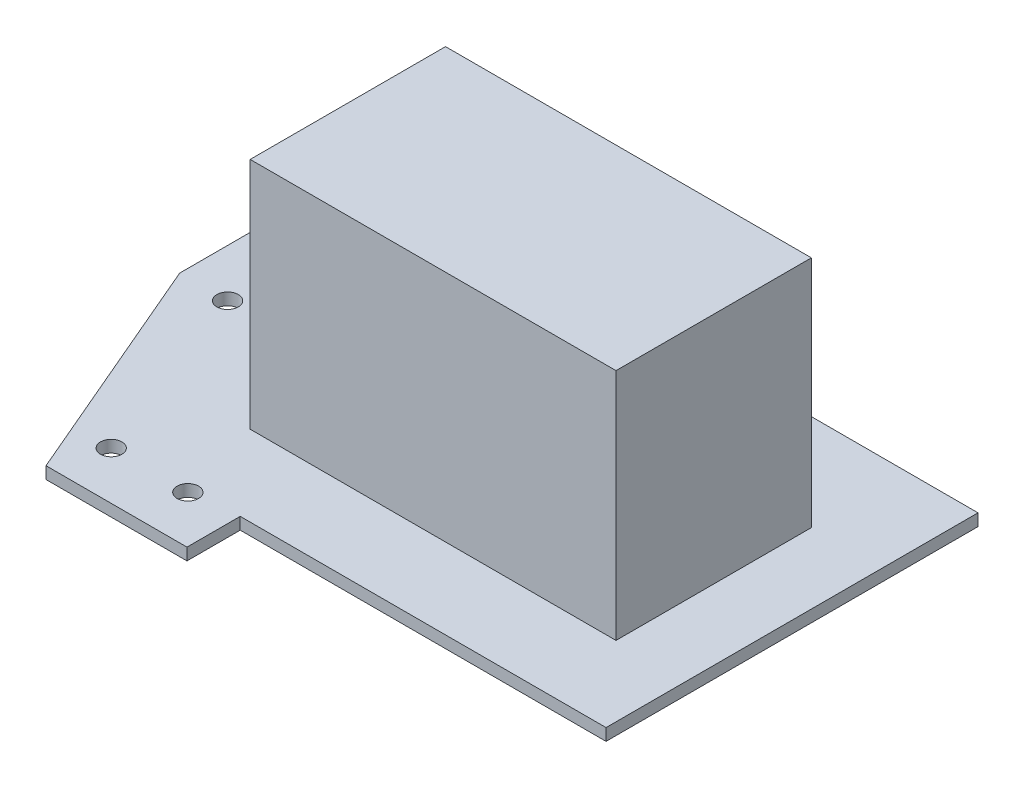
SolidWorks part; units mm, degrees
ref_plane "Front Plane" through (0, 0, 0) normal (0, 0, 1) x (1, 0, 0)
ref_plane "Top Plane" through (0, 0, 0) normal (0, 1, 0) x (1, 0, 0)
ref_plane "Right Plane" through (0, 0, 0) normal (1, 0, 0) x (0, 0, -1)
sketch "Sketch1" plane through (0, 0, 0) normal (0, 1, 0) x (1, 0, 0)
  line L0 (0, 0) -> (0, -25.4)
  line L1 (0, -25.4) -> (13.2588, -56.388)
  line L2 (13.2588, -56.388) -> (31.9532, -56.388)
  line L3 (31.9532, -56.388) -> (31.9532, -49.3268)
  line L4 (31.9532, -49.3268) -> (80.4672, -49.3268)
  line L5 (80.4672, -49.3268) -> (80.4672, 0)
  line L6 (80.4672, 0) -> (0, 0)
  dimension "D1" = 80.4672
  dimension "D2" = 49.3268
  dimension "D3" = 56.388
  dimension "D4" = 25.4
  dimension "D5" = 48.514
  dimension "D6" = 18.6944
extrude "Boss-Extrude1" add sketch "Sketch1" along normal blind 1.5875
sketch "Sketch2" plane through (0, 0, 0) normal (0, -1, 0) x (1, 0, 0)
  line L1 (36.068, 0) -> (0, 0)
  line L2 (36.068, 0) -> (36.068, 1.5875)
  line L3 (36.068, 1.5875) -> (0, 1.5875)
  line L4 (0, 0) -> (0, 1.5875)
  dimension "D1" = 1.5875
  dimension "D2" = 36.068
extrude "Boss-Extrude2" add sketch "Sketch2" along normal blind 21.2725
sketch "Sketch3" plane through (0, 0, 1.5875) normal (0, 0, 1) x (1, 0, 0)
  line L0 (36.068, -21.2725) -> (36.068, 0) construction
  line L1 (36.068, -9.144) -> (34.4805, -9.144)
  line L2 (36.068, -9.144) -> (36.068, -34.798)
  line L3 (36.068, -34.798) -> (34.4805, -34.798)
  line L4 (34.4805, -9.144) -> (34.4805, -34.798)
  line L5 (36.068, 0) -> (0, 0) construction
  line L7 (18.034, 0) -> (18.034, -21.2725) construction
  line L9 (36.068, -21.2725) -> (0, -21.2725) construction
  line L10 (1.5875, -9.144) -> (1.5875, -34.798)
  line L11 (0, -34.798) -> (1.5875, -34.798)
  line L12 (0, -9.144) -> (0, -34.798)
  line L13 (0, -9.144) -> (1.5875, -9.144)
  dimension "D1" = 1.5875
  dimension "D2" = 9.144
  dimension "D3" = 34.798
extrude "Boss-Extrude3" add sketch "Sketch3" along normal blind 6.35
fillet "Fillet1" radius 3.175 8 edges at (35.2742, -21.2725, 1.5875) (0.7937, -21.2725, 1.5875) (0.7937, -9.144, 7.9375) (0.7937, -34.798, 7.9375) (0.7937, -34.798, 1.5875) (35.2742, -9.144, 7.9375) (35.2743, -34.798, 1.5875) (35.2743, -34.798, 7.9375)
hole_wizard "Hole1" positions "Sketch6" profile "Sketch5" legacy
sketch "Sketch6" plane through (0, 0, 0) normal (0, 0, -1) x (-1, 0, 0)
  line L0 (-18.034, -21.2725) -> (-18.034, 1.5875) construction
  line L1 (-1.5875, -21.2725) -> (-34.4805, -21.2725) construction
  line L2 (-80.4672, 1.5875) -> (0, 1.5875) construction
  line L12 (0, -9.8425) -> (-80.4672, -9.8425) construction
  line L13 (0, -21.2725) -> (0, 1.5875) construction
  line L14 (-80.4672, 1.5875) -> (-80.4672, 0) construction
  point P0 (-18.034, -9.8425)
sketch "Sketch5" plane through (18.034, -9.8425, 0) normal (1, 0, 0) x (0, 1, 0)
  line L0 (0, 0) -> (0, 15.875)
  line L1 (0, 15.875) -> (2.54, 15.875)
  line L2 (2.54, 15.875) -> (2.54, 0)
  line L3 (2.54, 0) -> (0, 0)
  line L4 (0, 110) -> (0, -10) construction
  dimension "Diameter" = 5.08
  dimension "Depth" = 15.875
hole_wizard "Hole2" positions "Sketch8" profile "Sketch7" legacy end condition through all
sketch "Sketch8" plane through (36.068, 3.9375, -1.4555) normal (1, 0, 0) x (0, 0, -1)
  line L0 (-3.043, -35.5605) -> (-3.043, -27.9597) construction
  line L1 (-50.7823, -2.35) -> (-1.4555, -2.35) construction
  point P0 (-6.218, -32.05)
  dimension "D1" = 3.175
  dimension "D2" = 29.7
sketch "Sketch7" plane through (36.068, -28.1125, 4.7625) normal (0, 1, 0) x (0, 0, -1)
  line L0 (0, 0) -> (0, 36.068)
  line L1 (0, 36.068) -> (1.4224, 36.068)
  line L2 (1.4224, 36.068) -> (1.4224, 0)
  line L3 (1.4224, 0) -> (0, 0)
  line L4 (0, 110) -> (0, -10) construction
  dimension "Diameter" = 2.8448
  dimension "Depth" = 36.068
sketch "Sketch9" plane through (0, 1.5875, 0) normal (0, 1, 0) x (1, 0, 0)
  line L0 (0, 0) -> (0, -25.4) construction
  line L1 (71.12, -12.7508) -> (22.606, -12.7508)
  line L2 (71.12, -12.7508) -> (71.12, -38.6588)
  line L3 (71.12, -38.6588) -> (22.606, -38.6588)
  line L4 (22.606, -12.7508) -> (22.606, -38.6588)
  line L5 (31.9532, -49.3268) -> (80.4672, -49.3268) construction
  dimension "D1" = 48.514
  dimension "D2" = 25.908
  dimension "D3" = 22.606
  dimension "D4" = 10.668
extrude "Boss-Extrude4" add sketch "Sketch9" along normal blind 30.988
hole_wizard "Hole3" positions "Sketch11" profile "Sketch10" legacy end condition through all
sketch "Sketch11" plane through (0, 1.5875, 0) normal (0, 1, 0) x (-1, 0, 0)
  line L1 (-22.606, 56.388) -> (-22.606, 43.688) construction
  line L2 (-13.2588, 56.388) -> (-31.9532, 56.388) construction
  point P0 (-25.7175, 50.038)
  dimension "D1" = 12.7
  dimension "D2" = 3.1115
  dimension "D3" = 6.35
sketch "Sketch10" plane through (25.7175, 1.5875, 50.038) normal (1, 0, 0) x (0, 0, 1)
  line L0 (0, 0) -> (0, 36.3855)
  line L1 (0, 36.3855) -> (1.4224, 36.3855)
  line L2 (1.4224, 36.3855) -> (1.4224, 0)
  line L3 (1.4224, 0) -> (0, 0)
  line L4 (0, 110) -> (0, -10) construction
  dimension "Diameter" = 2.8448
  dimension "Depth" = 36.3855
pattern_linear "LPattern1" count 2 spacing 10.16 along (-1, 0, 0) of "Hole3"
hole_wizard "Hole4" positions "Sketch13" profile "Sketch12" legacy end condition through all
sketch "Sketch13" plane through (0, 1.5875, 0) normal (0, 1, 0) x (-1, 0, 0)
  line L0 (0, 0) -> (0, 25.4) construction
  line L1 (-80.4672, 0) -> (0, 0) construction
  point P0 (-6.35, 25.4)
  dimension "D1" = 6.35
  dimension "D2" = 25.4
sketch "Sketch12" plane through (6.35, 1.5875, 25.4) normal (1, 0, 0) x (0, 0, 1)
  line L0 (0, 0) -> (0, 36.3855)
  line L1 (0, 36.3855) -> (1.4224, 36.3855)
  line L2 (1.4224, 36.3855) -> (1.4224, 0)
  line L3 (1.4224, 0) -> (0, 0)
  line L4 (0, 110) -> (0, -10) construction
  dimension "Diameter" = 2.8448
  dimension "Depth" = 36.3855
pattern_linear "LPattern2" count 2 spacing 28.575 along (1, 0, 0) of "Hole4"
ref_point "Point1"
ref_point "Point2"
ref_point "Point3"
ref_point "Point4"
ref_point "Point5"
